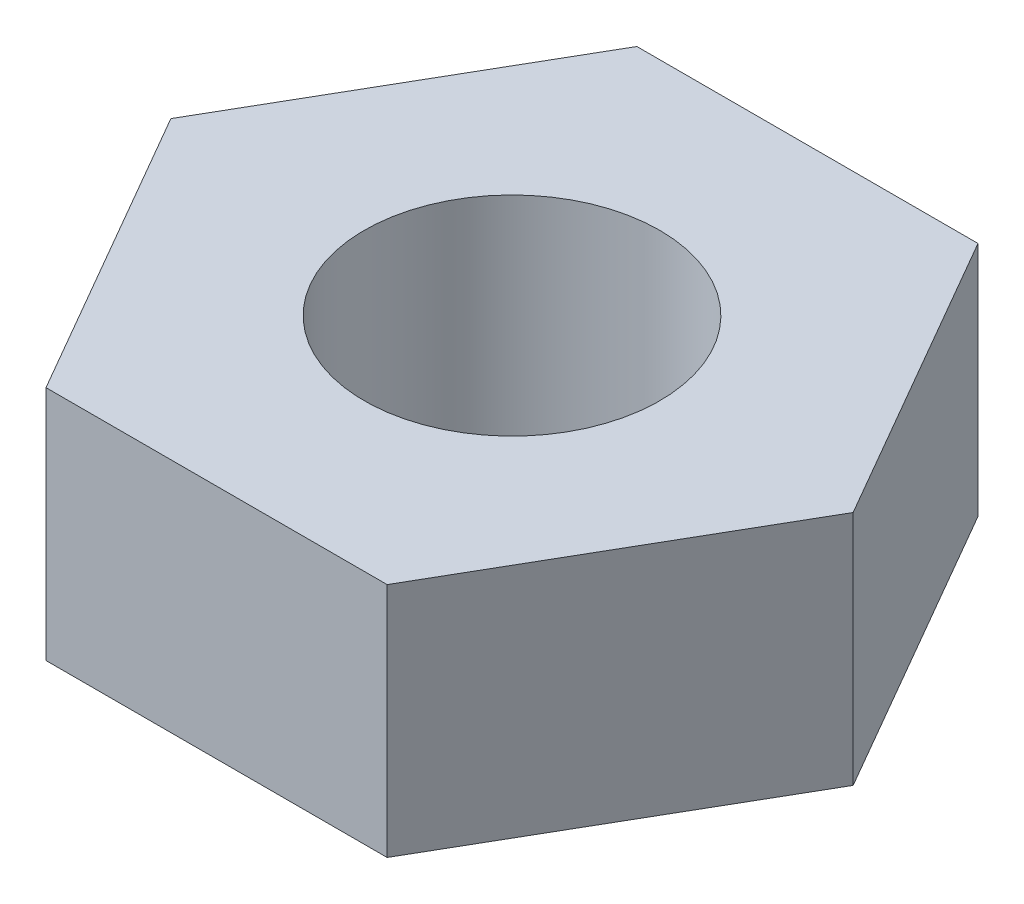
SolidWorks part; units mm, degrees
ref_plane "前视基准面" through (0, 0, 0) normal (0, 0, 1) x (1, 0, 0)
ref_plane "上视基准面" through (0, 0, 0) normal (0, 1, 0) x (1, 0, 0)
ref_plane "右视基准面" through (0, 0, 0) normal (1, 0, 0) x (0, 0, -1)
other "Configuration Table"
sketch "草图1" plane through (0, 0, 0) normal (0, 1, 0) x (1, 0, 0)
  line L1 (2.8868, 0) -> (1.4434, 2.5)
  line L2 (1.4434, 2.5) -> (-1.4434, 2.5)
  line L3 (-1.4434, 2.5) -> (-2.8868, 0)
  line L4 (-2.8868, 0) -> (-1.4434, -2.5)
  line L5 (-1.4434, -2.5) -> (1.4434, -2.5)
  line L6 (1.4434, -2.5) -> (2.8868, 0)
  circle A0 centre (0, 0) radius 2.5 construction
  dimension "D1" = 5
extrude "凸台-拉伸1" add sketch "草图1" along normal blind 2
sketch "草图3" plane through (0, 0, 0) normal (0, -1, 0) x (1, 0, 0)
  circle A0 centre (0, 0) radius 1.25
  dimension "D1" = 2.5
extrude "切除-拉伸1" cut sketch "草图3" against normal through all
ref_axis "基准轴1" through (0, 5.2881, 0) along (0, -1, 0)
